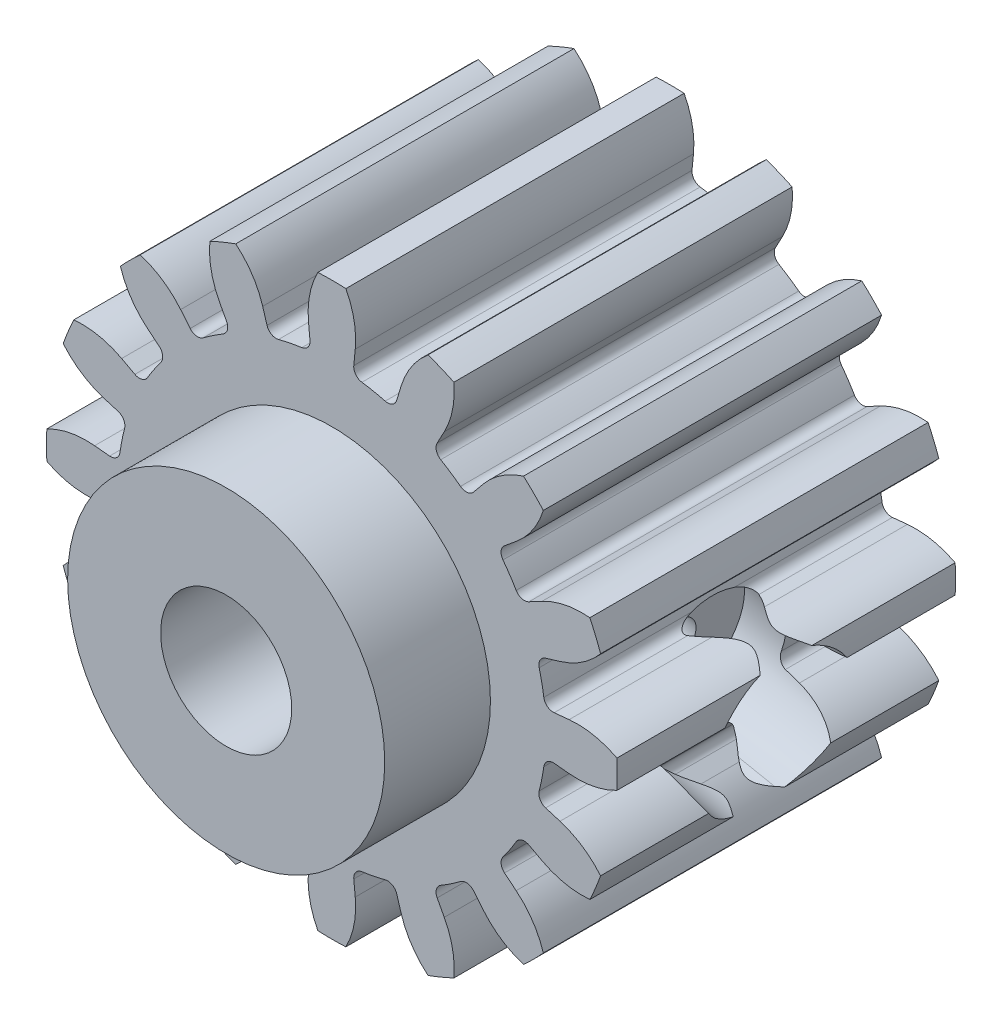
SolidWorks part; units mm, degrees
ref_plane "Front Plane" through (0, 0, 0) normal (0, 0, 1) x (1, 0, 0)
ref_plane "Top Plane" through (0, 0, 0) normal (0, 1, 0) x (1, 0, 0)
ref_plane "Right Plane" through (0, 0, 0) normal (1, 0, 0) x (0, 0, -1)
sketch "Esquisse1" plane through (0, 0, 0) normal (0, 0, 1) x (1, 0, 0)
  line L0 (0, 0) -> (22.1157, 0) construction
  line L1 (0, 0) -> (24.5207, 4.8775) construction
  line L2 (0, 0) -> (24.5207, -4.8775) construction
  line L3 (0, 0) -> (25.037, 2.4659) construction
  line L4 (0, 0) -> (9.9305, 1.9753)
  line L5 (0, 0) -> (19.7908, -1.9492) construction
  line L6 (0, 0) -> (9.9305, -1.9753)
  line L7 (0, 0) -> (17.8082, 0.8749) construction
  line L8 (10.0762, 0.9924) -> (11.222, 1.1053)
  line L9 (10.0762, -0.9924) -> (11.222, -1.1053)
  line L10 (0, 0) -> (17.7116, -0.8701) construction
  circle A0 centre (0, 0) radius 12 construction
  circle A1 centre (0, 0) radius 13.5 construction
  circle A2 centre (0, 0) radius 10.125 construction
  circle A3 centre (0, 0) radius 11.2763 construction
  arc A4 (9.9305, 1.9753) -> (10.0762, 0.9924) centre (0, 0) cw
  arc A5 (9.9305, -1.9753) -> (10.0762, -0.9924) centre (0, 0) ccw
  arc A6 (11.222, 1.1053) -> (13.4837, 0.6624) centre (11.615, -2.8846) cw
  arc A7 (13.4837, 0.6624) -> (13.4837, -0.6624) centre (0, 0) cw
  arc A8 (11.222, -1.1053) -> (13.4837, -0.6624) centre (11.615, 2.8846) ccw
  dimension "PrimitiveDiameter" = 24
  dimension "OutsideDiameter" = 27
  dimension "InternalDiameter" = 20.25
  dimension "BaseDiameter" = 22.5526
  dimension "DemiToothAngle" = 11.25
  dimension "QuartToothAngle" = 5.625
  dimension "D1" = 5.625
  dimension "D2" = 2.813
  dimension "D3" = 2.813
extrude "MainGear" add sketch "Esquisse1" along normal mid plane 16
fillet "Congé1" radius 0.45 2 edges at (10.0762, -0.9924, 0) (10.0762, 0.9924, 0)
ref_axis "Axe1" through (0, 0, 8) along (0, 0, -1)
pattern_circular "Répétition circulaire1" count 16 every 22.5 about axis through (0, 0, 8) along (0, 0, -1) of "MainGear", "Congé1"
sketch "Esquisse3" plane through (0, 0, -8) normal (0, 0, 1) x (1, 0, 0)
  circle A0 centre (0, 0) radius 3.1
  dimension "D1" = 6.2
sketch "Esquisse9" plane through (0, 0, 8) normal (0, 0, 1) x (1, 0, 0)
  circle A0 centre (0, 0) radius 7.5
  circle A2 centre (0, 0) radius 3.1
  dimension "D1" = 6.2
  dimension "D2" = 15
extrude "GearBottomFix" add sketch "Esquisse9" along normal blind 5
extrude "GearHole" cut sketch "Esquisse3" along normal through all
ref_plane "Plane1" through (0, 0, 0) normal (0.9808, -0.1951, 0) x (0, 0, -1)
sketch "Sketch1" plane through (0, 0, 0) normal (0.9808, -0.1951, 0) x (0, 0, -1)
  circle A0 centre (0, 0) radius 1.25
  dimension "D1" = 2.5
extrude "Cut-Extrude2" cut sketch "Sketch1" along normal through all both and the other way through all
ref_plane "Plane2" through (9.9151, -1.9722, 0) normal (0.9808, -0.1951, 0) x (0, 0, -1)
ref_plane "Plane3" through (7.9535, -1.5821, 0) normal (0.9808, -0.1951, 0) x (0, 0, -1)
sketch "Sketch2" plane through (7.9535, -1.5821, 0) normal (0.9808, -0.1951, 0) x (0, 0, -1)
  circle A0 centre (0, 0) radius 3.5
  dimension "D1" = 7
extrude "Cut-Extrude3" cut sketch "Sketch2" along normal through all
equation "\"Modulo\"= 1.5mm"
equation "\"ToothCount\"= 16"
equation "\"PrimitiveDiameter@Esquisse1\"= \"Modulo\" * \"ToothCount\""
equation "\"OutsideDiameter@Esquisse1\" = \"Modulo\" *  ( \"ToothCount\" + 2 ) "
equation "\"InternalDiameter@Esquisse1\" = \"PrimitiveDiameter@Esquisse1\" - \"Modulo\" * 2.5"
equation "\"Angle\"= 20deg"
equation "\"BaseDiameter@Esquisse1\" = \"PrimitiveDiameter@Esquisse1\" * cos ( \"Angle\" ) "
equation "\"DemiToothAngle@Esquisse1\" = 180 / \"ToothCount\""
equation "\"QuartToothAngle@Esquisse1\"= \"DemiToothAngle@Esquisse1\" / 2"
equation "\"D1@Esquisse1\"= \"QuartToothAngle@Esquisse1\""
equation "\"D2@Esquisse1\"= \"QuartToothAngle@Esquisse1\" / 2"
equation "\"D3@Esquisse1\"= \"D2@Esquisse1\""
equation "\"D2@Répétition circulaire1\"=360/\"ToothCount\""
equation "\"D1@Congé1\"=\"Modulo\"*0.3"
